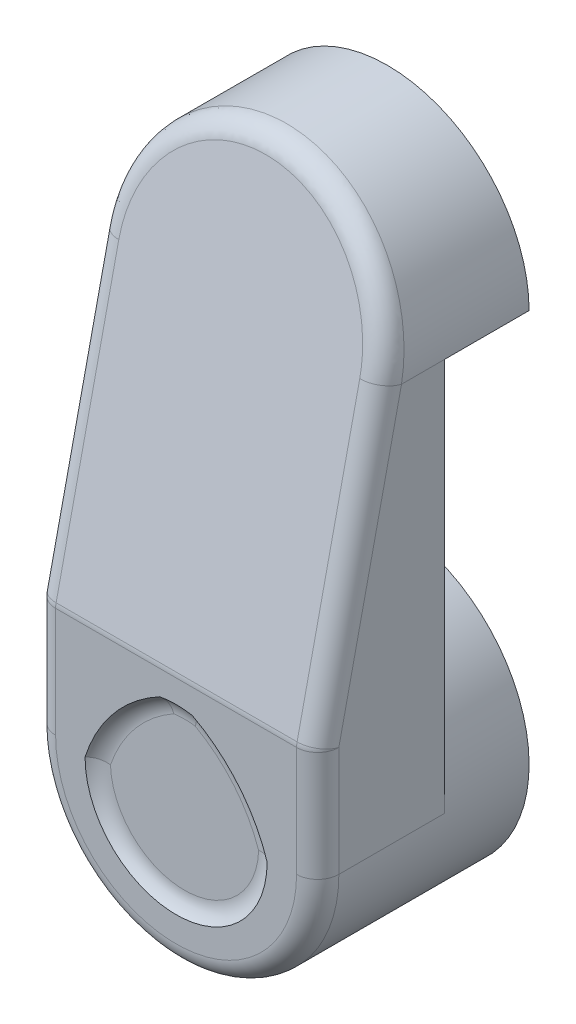
SolidWorks part; units mm, degrees
material "PET"
ref_plane "Front Plane" through (0, 0, 0) normal (0, 0, 1) x (1, 0, 0)
ref_plane "Top Plane" through (0, 0, 0) normal (0, 1, 0) x (1, 0, 0)
ref_plane "Right Plane" through (0, 0, 0) normal (1, 0, 0) x (0, 0, -1)
sketch "Sketch2" plane through (0, 0, 0) normal (0, 0, 1) x (1, 0, 0)
  line L0 (0, -4.65) -> (0, 4.65) construction
  line L1 (-3.35, -4.65) -> (-3.35, 4.65)
  line L2 (3.35, -4.65) -> (3.35, 4.65)
  arc A0 (-3.35, -4.65) -> (3.35, -4.65) centre (0, -4.65) ccw
  arc A1 (3.35, 4.65) -> (-3.35, 4.65) centre (0, 4.65) ccw
  point P2 (0, 0)
  dimension "D1" = 16
  dimension "D2" = 6.7
extrude "Boss-Extrude1" add sketch "Sketch2" against normal blind 5
fillet "Fillet1" radius 0.5 4 edges at (0, -8, 0) (-3.35, 0, 0) (0, 8, 0) (3.35, 0, 0)
sketch "Sketch4" plane through (0, 0, 0) normal (1, 0, 0) x (0, 0, -1)
  line L0 (5, 8) -> (2.2119, 8) construction
  line L1 (5, 8) -> (0.5, 8) construction
  line L2 (2.2119, 8) -> (0, -1.9946) construction
  line L3 (0, 4.65) -> (0, -4.65) construction
  line L4 (0, -1.9946) -> (0, -7.5) construction
  line L5 (2.2119, 8) -> (0.5, 8)
  line L6 (0, -1.9946) -> (0, 7.5)
  line L7 (0, 7.5) -> (0, 4.65) construction
  line L8 (2.2119, 8) -> (0, -1.9946)
  arc A0 (0.5, 8) -> (0, 7.5) centre (0.5, 7.5) ccw construction
  arc A1 (0, 7.5) -> (0.5, 8) centre (0.5, 7.5) cw
extrude "Cut-Extrude1" cut sketch "Sketch4" against normal through all both and the other way through all
sketch "Sketch5" plane through (0, 0, 0) normal (0, 0, 1) x (1, 0, 0)
  line L0 (0, -1.9946) -> (0, -7.5) construction
  line L1 (-2.85, -1.9946) -> (2.85, -1.9946) construction
  line L2 (0, -4.7473) -> (-1.3985, -4.7473) construction
  arc A0 (-2.85, -4.65) -> (2.85, -4.65) centre (0, -4.65) ccw construction
  arc A1 (-2.1539, -4.7473) -> (2.1539, -4.7473) centre (0, -4.7473) ccw
  arc A2 (-2.1539, -4.7473) -> (-0.3851, -2.6281) centre (1.3403, -5.866) cw
  arc A3 (2.1539, -4.7473) -> (0.3851, -2.6281) centre (-1.3403, -5.866) ccw
  arc A4 (0.3851, -2.6281) -> (-0.3851, -2.6281) centre (0, -4.7473) ccw
  point P9 (0.4646, -2.1907)
  point P16 (2.2688, -4.7473)
  point P17 (-2.1539, -4.7473)
extrude "Cut-Extrude2" cut sketch "Sketch5" against normal blind 0.2
fillet "Fillet2" radius 0.5 4 edges at (0, -6.9012, -0.2) (0, -2.5934, -0.2) (-1.4764, -3.515, -0.2) (1.4764, -3.515, -0.2)
fillet "Fillet4" radius 0.5 6 edges at (3.35, 2.4573, -0.9853) (3.2036, -1.3329, -0.1464) (-3.2036, -1.3329, -0.1464) (-3.35, 2.4573, -0.9853) (0, -1.9946, 0) (0, 8, -2.2119)
sketch "Sketch7" plane through (0, 0, -5) normal (0, 0, -1) x (-1, 0, 0)
  line L0 (-2.85, 4.65) -> (-2.85, -4.65)
  line L1 (2.85, -4.65) -> (2.85, 4.65)
  line L2 (3.35, -4.65) -> (3.35, 4.65)
  line L3 (-3.35, 4.65) -> (-3.35, -4.65)
  line L4 (3.35, -4.65) -> (3.35, 4.65) construction
  line L5 (-3.35, 4.65) -> (-3.35, -4.65) construction
  arc A0 (-2.85, -4.65) -> (2.85, -4.65) centre (0, -4.65) ccw
  arc A1 (2.85, 4.65) -> (-2.85, 4.65) centre (0, 4.65) ccw
  arc A2 (-3.35, -4.65) -> (3.35, -4.65) centre (0, -4.65) ccw
  arc A3 (3.35, 4.65) -> (-3.35, 4.65) centre (0, 4.65) ccw
  arc A4 (-3.35, -4.65) -> (3.35, -4.65) centre (0, -4.65) ccw construction
  arc A5 (3.35, 4.65) -> (-3.35, 4.65) centre (0, 4.65) ccw construction
  dimension "D1" = 0
  dimension "D2" = 0.5
extrude "Cut-Extrude4" cut sketch "Sketch7" against normal blind 2
sketch "Sketch8" plane through (0, 0, 0) normal (1, 0, 0) x (0, 0, -1)
  line L0 (5, 4.65) -> (3, 4.65)
  line L1 (5, 4.65) -> (1.9826, 4.65) construction
  line L2 (3, 4.65) -> (3, -9.2418)
  line L3 (3, -9.2418) -> (5, -9.2418)
  line L4 (5, -9.2418) -> (5, 4.65)
  dimension "D1" = 2
extrude "Cut-Extrude5" cut sketch "Sketch8" against normal through all both and the other way through all
sketch "Sketch9" plane through (0, 0, -3) normal (0, 0, -1) x (-1, 0, 0)
  circle A0 centre (0, -4.65) radius 3.35
extrude "Boss-Extrude3" add sketch "Sketch9" along normal up to surface (2 mm away) up to face at (0, 6.2, -5)
sketch "Sketch10" plane through (0, 0, -3) normal (0, 0, -1) x (-1, 0, 0)
  line L1 (-0.25, -1.8992) -> (0.25, -1.8992)
  line L2 (-0.25, -1.8992) -> (-0.25, 7.6868)
  line L3 (-0.25, 7.6868) -> (0.25, 7.6868)
  line L4 (0.25, -1.8992) -> (0.25, 7.6868)
  dimension "D1" = 0.25
  dimension "D2" = 0.5
extrude "Boss-Extrude4" add sketch "Sketch10" along normal up to surface (2 mm away) up to face at (0, 6.2, -5)
